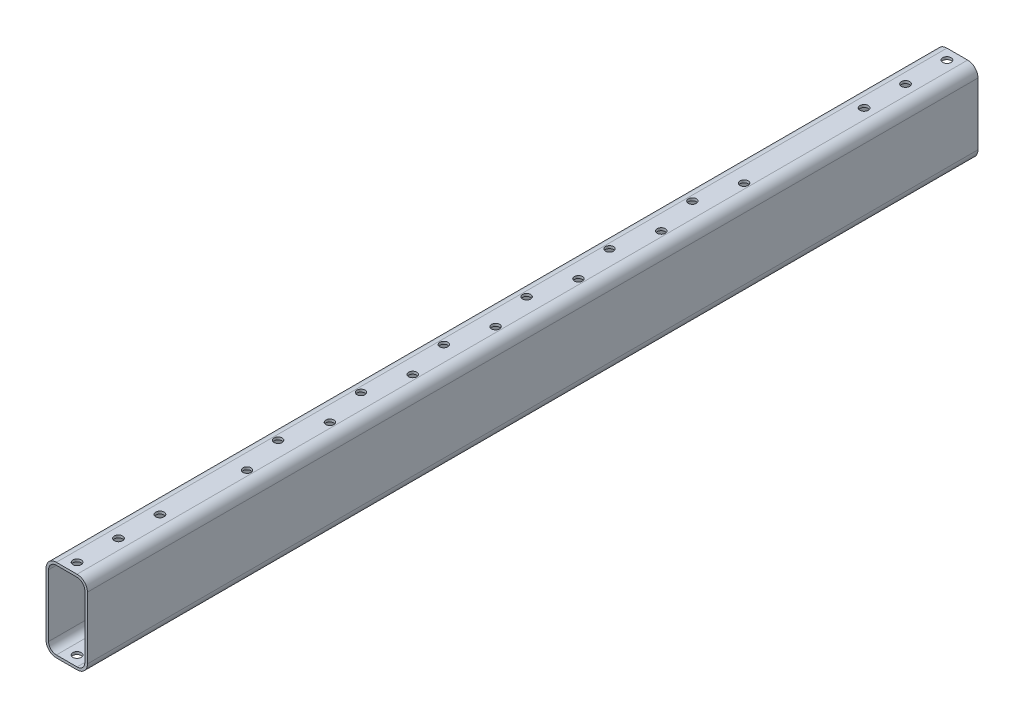
SolidWorks part; units mm, degrees
material "6061-T6 (SS)"
ref_plane "Front Plane" through (0, 0, 0) normal (0, 0, 1) x (1, 0, 0)
ref_plane "Top Plane" through (0, 0, 0) normal (0, 1, 0) x (1, 0, 0)
ref_plane "Right Plane" through (0, 0, 0) normal (1, 0, 0) x (0, 0, -1)
sketch "Sketch1" plane through (0, 0, 0) normal (0, 0, 1) x (1, 0, 0)
  line L1 (-6.35, -25.4) -> (6.35, -25.4)
  line L2 (-12.7, -19.05) -> (-12.7, 19.05)
  line L3 (-6.35, 25.4) -> (6.35, 25.4)
  line L4 (12.7, -19.05) -> (12.7, 19.05)
  line L5 (-12.7, -25.4) -> (12.7, 25.4) construction
  line L6 (-12.7, 25.4) -> (12.7, -25.4) construction
  arc A0 (-12.7, -19.05) -> (-6.35, -25.4) centre (-6.35, -19.05) ccw
  arc A1 (6.35, -25.4) -> (12.7, -19.05) centre (6.35, -19.05) ccw
  arc A2 (6.35, 25.4) -> (12.7, 19.05) centre (6.35, 19.05) cw
  arc A3 (-12.7, 19.05) -> (-6.35, 25.4) centre (-6.35, 19.05) cw
  point P0 (0, 0)
  dimension "D3" = 6.35
  dimension "D1" = 50.8
  dimension "D2" = 25.4
extrude "Extrude-Thin1" add sketch "Sketch1" along normal blind 546.1 thin thin type one direction reverse wall 1.5875
hole_wizard "#10 Clearance Hole1" positions "3DSketch1" profile "Sketch3" hole size "#10" standard "ANSI Inch" end condition through all
sketch3d "3DSketch1"
  line L1 (6.35, 25.4, 0) -> (-6.35, 25.4, 0) construction
  line L6 (0, 25.4, 546.1) -> (0, 25.4, 0) construction
  line L7 (6.35, 25.4, 546.1) -> (-6.35, 25.4, 546.1) construction
  point P57 (0, 25.4, 6.35)
  point P59 (0, 25.4, 31.75)
  point P61 (0, 25.4, 57.15)
  point P63 (0, 25.4, 514.35)
  point P65 (0, 25.4, 488.95)
  point P67 (0, 25.4, 539.75)
  dimension "D1" = 25.4
  dimension "D2" = 25.4
  dimension "D3" = 6.35
  dimension "D4" = 25.4
  dimension "D5" = 25.4
  dimension "D6" = 6.35
sketch "Sketch3" plane through (0, 25.4, 539.75) normal (1, 0, 0) x (0, 0, 1)
  line L0 (0, 0) -> (0, 50.8)
  line L1 (0, 50.8) -> (2.5527, 50.8)
  line L2 (2.5527, 50.8) -> (2.5527, 0)
  line L5 (2.5527, 0) -> (0, 0)
  line L11 (0, -6.35) -> (0, 107.95) construction
  dimension "Thru Hole Dia." = 5.1054
  dimension "Thru Hole Depth" = 50.8
hole_wizard "3/16 (0.195) Diameter Hole1" positions "Sketch4" profile "Sketch5" hole size "3/16" standard "ANSI Inch" end condition up to next
sketch "Sketch4" plane through (0, 25.4, 0) normal (0, 1, 0) x (1, 0, 0)
  point P0 (3.175, -438.6947)
  point P3 (-3.175, -413.2947)
  point P6 (3.175, -387.8947)
  point P9 (-3.175, -362.4947)
  point P12 (3.175, -337.0947)
  point P15 (-3.175, -311.6947)
  point P18 (3.175, -286.2947)
  point P21 (-3.175, -260.8947)
  point P24 (3.175, -235.4947)
  point P29 (3.175, -184.6947)
  point P32 (-3.175, -159.2947)
  point P35 (3.175, -133.8947)
  point P41 (-3.175, -210.0947)
sketch "Sketch5" plane through (3.175, 25.4, 438.6947) normal (1, 0, 0) x (0, 0, 1)
  line L0 (0, 0) -> (0, 1.5875)
  line L1 (0, 1.5875) -> (2.4765, 1.5875)
  line L2 (2.4765, 1.5875) -> (2.4765, 0)
  line L5 (2.4765, 0) -> (0, 0)
  line L11 (0, -6.35) -> (0, 107.95) construction
  dimension "Thru Hole Dia." = 4.953
  dimension "Thru Hole Depth" = 1.5875
